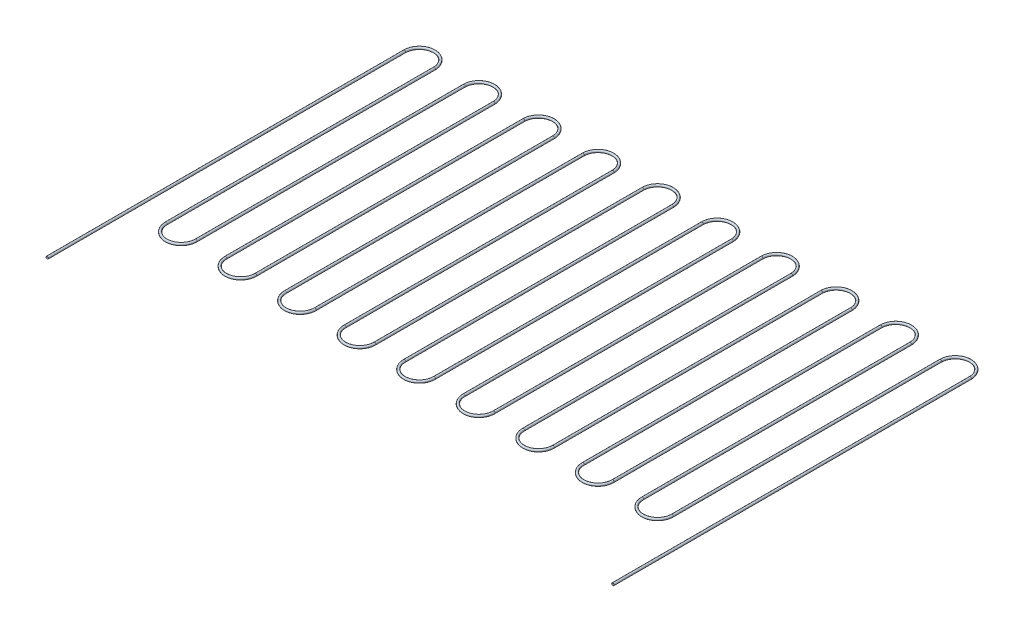
SolidWorks part; units mm, degrees
ref_plane "Front Plane" through (0, 0, 0) normal (0, 0, 1) x (1, 0, 0)
ref_plane "Top Plane" through (0, 0, 0) normal (0, 1, 0) x (1, 0, 0)
ref_plane "Right Plane" through (0, 0, 0) normal (1, 0, 0) x (0, 0, -1)
sketch "Sketch4" plane through (0, 0, 0) normal (0, 1, 0) x (1, 0, 0)
  line L0 (950, -450) -> (950, 450)
  line L5 (850, -450) -> (850, 450)
  line L6 (750, -450) -> (750, 450)
  line L7 (650, -450) -> (650, 450)
  line L8 (550, -450) -> (550, 450)
  line L9 (450, -450) -> (450, 450)
  line L10 (350, -450) -> (350, 450)
  line L11 (250, -450) -> (250, 450)
  line L12 (150, -450) -> (150, 450)
  line L13 (50, -450) -> (50, 450)
  line L14 (-50, -450) -> (-50, 450)
  line L15 (-150, -450) -> (-150, 450)
  line L16 (-250, -450) -> (-250, 450)
  line L17 (-350, -450) -> (-350, 450)
  line L18 (-450, -450) -> (-450, 450)
  line L19 (-550, -450) -> (-550, 450)
  line L20 (-650, -450) -> (-650, 450)
  line L21 (-750, -450) -> (-750, 450)
  line L22 (-850, -450) -> (-850, 450)
  line L23 (-950, -450) -> (-950, 450)
  line L24 (-950, -450) -> (-950, -750)
  line L25 (950, -450) -> (950, -750)
  line L27 (50, 0) -> (-49950, 0) construction
  arc A0 (950, 450) -> (850, 450) centre (900, 450) ccw
  arc A1 (750, 450) -> (650, 450) centre (700, 450) ccw
  arc A2 (550, 450) -> (450, 450) centre (500, 450) ccw
  arc A3 (350, 450) -> (250, 450) centre (300, 450) ccw
  arc A4 (50, 450) -> (150, 450) centre (100, 450) cw
  arc A5 (-150, 450) -> (-50, 450) centre (-100, 450) cw
  arc A6 (-350, 450) -> (-250, 450) centre (-300, 450) cw
  arc A7 (-550, 450) -> (-450, 450) centre (-500, 450) cw
  arc A8 (-650, 450) -> (-750, 450) centre (-700, 450) ccw
  arc A9 (-750, -450) -> (-850, -450) centre (-800, -450) cw
  arc A10 (-550, -450) -> (-650, -450) centre (-600, -450) cw
  arc A11 (-350, -450) -> (-450, -450) centre (-400, -450) cw
  arc A12 (-150, -450) -> (-250, -450) centre (-200, -450) cw
  arc A13 (-50, -450) -> (50, -450) centre (0, -450) ccw
  arc A14 (150, -450) -> (250, -450) centre (200, -450) ccw
  arc A15 (350, -450) -> (450, -450) centre (400, -450) ccw
  arc A16 (650, -450) -> (550, -450) centre (600, -450) cw
  arc A17 (750, -450) -> (850, -450) centre (800, -450) ccw
  arc A18 (-850, 450) -> (-950, 450) centre (-900, 450) ccw
  point P67 (50, 0)
  dimension "D8" = 300
  dimension "D6" = 100
  dimension "D4" = 900
  dimension "D3" = 20
sweep "Sweep-Thin1" add path "Sketch4" circular profile diameter 7.9375 parameters "D1"=0.35, "D3"=7.9375
equation "\"absorber_plate_width\" = 1100mm"
equation "\"absorber_plate_length\" = 2100mm"
equation "\"absorber_plate_thickness\" = .1875in"
equation "\"groove_depth\" = 20mm"
equation "\"frame_thickness\" = 60mm"
equation "\"insulation_thickness\" = 50mm"
equation "\"glass_thickness\" = 3mm"
equation "\"pipe_distances\" = 100mm"
equation "\"pipe_OD\" = 0.3125in"
equation "\"pipe_ID\" = 0.249in"
equation "\"D6@Sketch4\"=\"pipe_distances\""
equation "\"D3@Sweep-Thin1\"=\"pipe_OD\""
equation "\"pipe_straight_length\" = 900mm"
equation "\"absorber_to_glass\" = 25mm"
equation "\"serpentine_length\" = 1900mm"
equation "\"wood_width\" = 3.5in"
equation "\"wood_height\" = 1.5in"
equation "\"D4@Sketch4\"=\"pipe_straight_length\""
